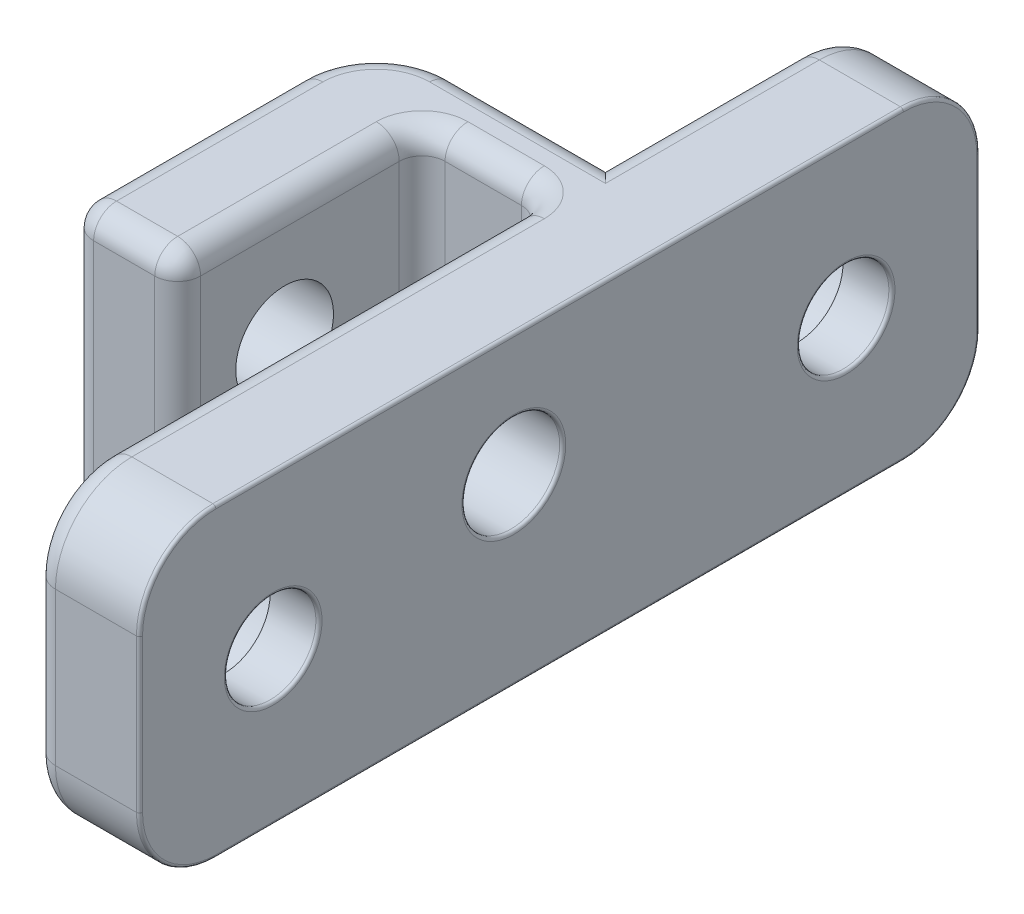
SolidWorks part; units mm, degrees
ref_plane "Front Plane" through (0, 0, 0) normal (0, 0, 1) x (1, 0, 0)
ref_plane "Top Plane" through (0, 0, 0) normal (0, 1, 0) x (1, 0, 0)
ref_plane "Right Plane" through (0, 0, 0) normal (1, 0, 0) x (0, 0, -1)
sketch "Sketch1" plane through (0, 0, 0) normal (0, 1, 0) x (1, 0, 0)
  line L0 (11, 30.5) -> (11, -24.5)
  line L1 (11, -24.5) -> (4, -24.5)
  line L2 (4, -24.5) -> (4, 9)
  line L3 (4, 9) -> (-4, 9)
  line L5 (-4, -7) -> (-11, -7)
  line L6 (-11, -7) -> (-11, 13)
  line L8 (4, 13) -> (4, 30.5)
  line L9 (4, 30.5) -> (11, 30.5)
  line L10 (4, 13) -> (-11, 13)
  line L11 (0, 3) -> (0, -3) construction
  line L12 (-9, 3) -> (11, 3) construction
  line L13 (-9, 3) -> (-9, -3) construction
  line L14 (-9, -3) -> (11, -3) construction
  line L15 (11, 3) -> (11, -3) construction
  line L16 (-4, 9) -> (-4, -7)
  line L17 (-4, -7) -> (4, -7)
  point P10 (0, 0)
  point P11 (0, 0)
  point P20 (0, 9)
  dimension "D1" = 5
  dimension "D2" = 2
  dimension "D3" = 8
  dimension "D4" = 6
  dimension "D5" = 7
  dimension "D6" = 4
  dimension "D7" = 6
  dimension "D8" = 4
  dimension "D9" = 17.5
  dimension "D10" = 17.5
extrude "Boss-Extrude1" add sketch "Sketch1" along normal mid plane 20 contours L16 L3 L2 L1 L0 L9 L8 L10 L6 L5 region at (10.4076, 0, -3)
extrude "Boss-Extrude2" add sketch "Sketch1<3>" along normal offset from surface (4 mm away) 16 from surface contours L16 L17 L2 L3 region at (0, 0, -1) up to face at (0.8, 10, -4.2) starting at face at (0.8, -10, -4.2)
sketch "Sketch1<3>" plane through (0, 0, 0) normal (0, 1, 0) x (1, 0, 0) same geometry as "Sketch1"
sketch "Sketch2" plane through (11, 0, 0) normal (1, 0, 0) x (0, 0, -1)
  line L0 (0, 10) -> (0, -10) construction
  line L1 (30.5, 10) -> (-24.5, 10) construction
  line L2 (30.5, -10) -> (-24.5, -10) construction
  line L3 (-24.5, 10) -> (-24.5, -10) construction
  line L4 (30.5, 10) -> (30.5, -10) construction
  circle A0 centre (0, 2) radius 3.2
  circle A1 centre (-15.75, 0) radius 3
  circle A2 centre (-15.75, 0) radius 4.75
  circle A3 centre (21.75, 0) radius 3
  circle A4 centre (21.75, 0) radius 4.75
  dimension "D1" = 6.4
  dimension "D2" = 9.5
  dimension "D3" = 4
  dimension "D4" = 6
  dimension "D5" = 4
  dimension "D6" = 8
extrude "Cut-Extrude1" cut sketch "Sketch2" against normal offset from surface (20 mm away) 2 contours A0 L0 | L0 A0 region at (11, 2, -1.3581) region at (11, 2, 1.3581) up to face at (-11, 0, -3)
extrude "Cut-Extrude2" cut sketch "Sketch2<4>" against normal up to next contours A1 | A3 region at (11, 0, 15.75) region at (11, 0, -21.75)
sketch "Sketch2<4>" plane through (11, 0, 0) normal (1, 0, 0) x (0, 0, -1) same geometry as "Sketch2"
extrude "Cut-Extrude3" cut sketch "Sketch2<5>" along normal offset from surface (3.8 mm away) 3.2 from surface contours A2 A1 | A4 A3 region at (11, 0, 20.3656) region at (11, 0, -17.1344) up to face at (11, 0, 12.75) starting at face at (4, 0, 18.75)
sketch "Sketch2<5>" plane through (11, 0, 0) normal (1, 0, 0) x (0, 0, -1) same geometry as "Sketch2"
sketch "Sketch3" plane through (11, 0, 0) normal (1, 0, 0) x (0, 0, -1)
  line L1 (-1.5, -1.2) -> (1.5, -1.2)
  line L2 (-1.5, -1.2) -> (-1.5, 5.2)
  line L3 (-1.5, 5.2) -> (1.5, 5.2)
  line L4 (1.5, -1.2) -> (1.5, 5.2)
  line L5 (-1.5, -1.2) -> (1.5, 5.2) construction
  line L6 (-1.5, 5.2) -> (1.5, -1.2) construction
  line L7 (-3.2, 0.5) -> (3.2, 0.5)
  line L8 (-3.2, 0.5) -> (-3.2, 3.5)
  line L9 (-3.2, 3.5) -> (3.2, 3.5)
  line L10 (3.2, 0.5) -> (3.2, 3.5)
  line L11 (-3.2, 0.5) -> (3.2, 3.5) construction
  line L12 (-3.2, 3.5) -> (3.2, 0.5) construction
  circle A0 centre (0, 2) radius 3.2 construction
  circle A1 centre (0, 2) radius 3.2
  circle M12 centre (0, 2) radius 3.2
  dimension "D1" = 1.5
extrude "Cut-Extrude4" cut sketch "Sketch3" against normal blind 0.3 from surface contours L9 L2 L7 L4 | L9 L4 L7 M12 | L9 L7 L2 M12 region at (11, 2, 2.2932) region at (11, 2, 0) region at (11, 2, -2.2932) starting at face at (-9, 2, 3.2)
extrude "Cut-Extrude5" cut sketch "Sketch3<3>" against normal blind 0.3 from surface contours L9 L2 L7 L4 region at (11, 2, 0) starting at face at (-9.3, 2, 0)
sketch "Sketch3<3>" plane through (11, 0, 0) normal (1, 0, 0) x (0, 0, -1) same geometry as "Sketch3"
fillet "Fillet1" radius 5 5 edges at (-11, 0, -13) (7.5, 10, -30.5) (7.5, -10, -30.5) (7.5, -10, 24.5) (7.5, 10, 24.5)
fillet "Fillet2" radius 1.5 29 edges at (-3.5, -10, 7) (4, -6, -1) (-1, -10, -13) (-9.5355, -10, -11.5355) (-1, 10, -13) (-9.5355, 10, -11.5355) (4, -10, 13.25) (4, -8.5355, 23.0355) (4, 0, 24.5) (4, 8.5355, 23.0355) (4, -10, -19.25) (4, -8.5355, -29.0355) (4, 0, -30.5) (4, 8.5355, -29.0355) (-7.5, 10, 7) (-11, -10, -0.5) (4, 2, -9) (-4, 2, -9) (0, -6, -9) (-4, -6, -1) (0, -6, 7) (-4, 2, 7) (-11, 0, 7) (-4, 10, -1) (0, 10, -9) (-11, 10, -0.5) (4, 10, 5.25) (4, 10, -19.25) (4, -8, 7)
fillet "Fillet4" radius 1 2 edges at (4, 0, 20.5) (4, 0, -17)
fillet "Fillet3" radius 0.2 11 edges at (11, -8.5355, -29.0355) (11, -10, -3) (11, -8.5355, 23.0355) (11, 0, 24.5) (11, 8.5355, 23.0355) (11, 10, -3) (11, 8.5355, -29.0355) (11, 0, -30.5) (11, 2, -3.2) (11, 0, -24.75) (11, 0, 12.75)
